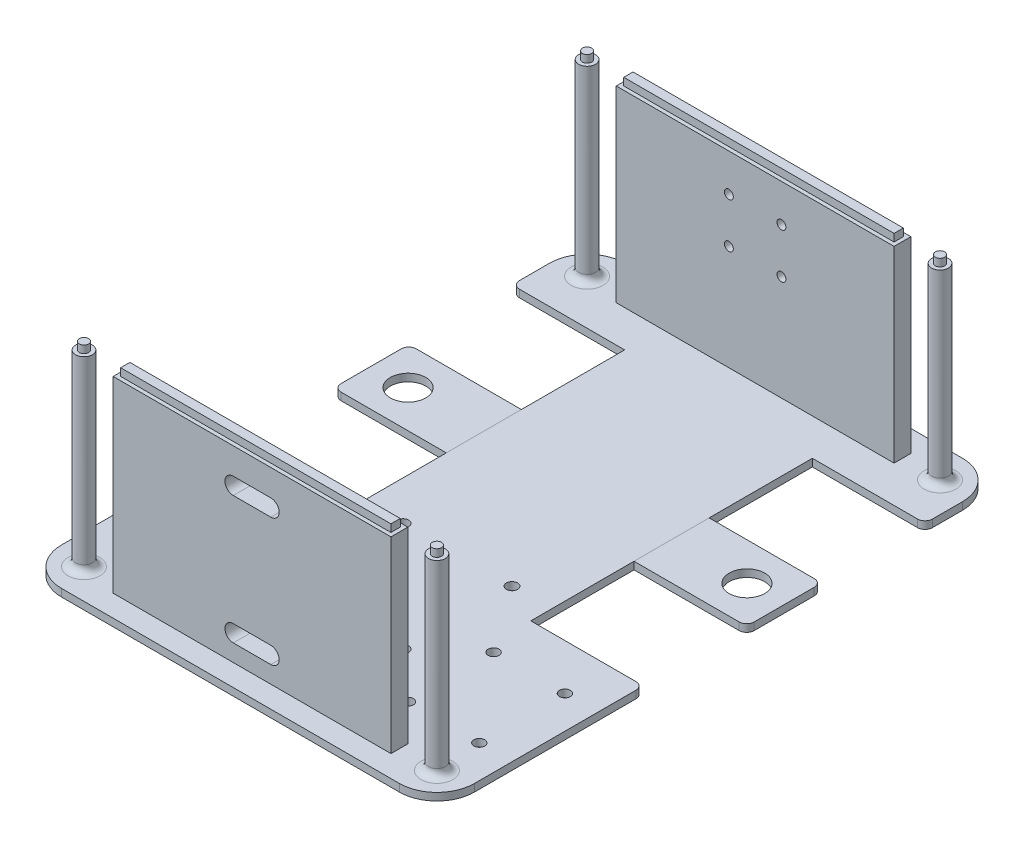
SolidWorks part; units mm, degrees
material "ABS"
ref_plane "Front Plane" through (0, 0, 0) normal (0, 0, 1) x (1, 0, 0)
ref_plane "Top Plane" through (0, 0, 0) normal (0, 1, 0) x (1, 0, 0)
ref_plane "Right Plane" through (0, 0, 0) normal (1, 0, 0) x (0, 0, -1)
sketch "Sketch2" plane through (0, 0, 0) normal (0, 1, 0) x (1, 0, 0)
  line L0 (-148.7583, 0) -> (98.0966, 0) construction
  line L1 (-69.85, -95.25) -> (69.85, -95.25)
  line L2 (-69.85, -95.25) -> (-69.85, 95.25)
  line L3 (-69.85, 95.25) -> (69.85, 95.25)
  line L4 (69.85, -95.25) -> (69.85, 95.25)
  line L5 (-69.85, -95.25) -> (69.85, 95.25) construction
  line L6 (-69.85, 95.25) -> (69.85, -95.25) construction
  line L7 (0, 121.1686) -> (0, -125.6862) construction
  point P0 (0, 0)
  dimension "D1" = 190.5
  dimension "D2" = 139.7
extrude "Base Plate" add sketch "Sketch2" along normal blind 2.54
sketch "Sketch4" plane through (0, 2.54, 0) normal (0, 1, 0) x (1, 0, 0)
  line L0 (0, -95.25) -> (0, 95.25) construction
  line L1 (-69.85, -95.25) -> (69.85, -95.25) construction
  line L2 (69.85, 95.25) -> (-69.85, 95.25) construction
  line L3 (-34.66, -69.85) -> (-34.66, -40.894) construction
  line L4 (-34.66, -40.894) -> (-58.79, -40.894) construction
  line L5 (-58.79, -40.894) -> (-58.79, -69.85) construction
  line L6 (-58.79, -69.85) -> (-34.66, -69.85) construction
  line L7 (69.85, -95.25) -> (69.85, 95.25) construction
  line L8 (-69.85, 95.25) -> (-69.85, -95.25) construction
  circle A0 centre (-58.79, -69.85) radius 1.8415
  circle A1 centre (-34.66, -69.85) radius 1.8415
  circle A2 centre (-34.66, -40.894) radius 1.8415
  circle A3 centre (-58.79, -40.894) radius 1.8415
  circle A4 centre (34.66, -69.85) radius 1.8415
  circle A5 centre (58.79, -69.85) radius 1.8415
  circle A6 centre (58.79, -40.894) radius 1.8415
  circle A7 centre (34.66, -40.894) radius 1.8415
  point P0 (-58.79, -69.85)
  point P1 (-58.79, -40.894)
  point P2 (-34.66, -40.894)
  point P3 (-34.66, -69.85)
  dimension "D4" = 3.683
  dimension "D1" = 28.956
  dimension "D2" = 24.13
  dimension "D3" = 11.06
  dimension "D5" = 25.4
extrude "L-Bracket holes" cut sketch "Sketch4" against normal blind 6.35
sketch "Sketch5" plane through (0, 2.54, 0) normal (0, 1, 0) x (1, 0, 0)
  line L0 (-69.85, -25.4) -> (-31.75, -25.4)
  line L1 (-69.85, 95.25) -> (-69.85, -95.25) construction
  line L2 (-31.75, -25.4) -> (-31.75, 69.85)
  line L3 (-31.75, 69.85) -> (-69.85, 69.85)
  line L4 (-69.85, 69.85) -> (-69.85, -25.4)
  line L5 (-69.85, -95.25) -> (69.85, -95.25) construction
  line L6 (69.85, 95.25) -> (-69.85, 95.25) construction
  line L7 (0, -95.25) -> (0, 95.25) construction
  line L8 (-58.79, -40.894) -> (-34.66, -40.894) construction
  line L9 (31.75, 69.85) -> (69.85, 69.85)
  line L10 (31.75, -25.4) -> (31.75, 69.85)
  line L11 (69.85, -25.4) -> (31.75, -25.4)
  line L12 (69.85, 69.85) -> (69.85, -25.4)
  dimension "D1" = 25.4
  dimension "D2" = 95.25
  dimension "D3" = 38.1
extrude "Steering Wheels Holes" cut sketch "Sketch5" against normal blind 6.35
fillet "Fillet1" radius 12.7 4 edges at (69.85, 1.27, -95.25) (-69.85, 1.27, -95.25) (69.85, 1.27, 95.25) (-69.85, 1.27, 95.25)
fillet "Fillet2" radius 2.54 4 edges at (69.85, 1.27, -69.85) (69.85, 1.27, 25.4) (-69.85, 1.27, 25.4) (-69.85, 1.27, -69.85)
sketch "Sketch6" plane through (0, 2.54, 0) normal (0, 1, 0) x (1, 0, 0)
  line L0 (-69.85, -95.25) -> (-69.85, 95.25) construction
  line L1 (-69.85, -95.25) -> (69.85, -95.25) construction
  line L2 (0, -88.935) -> (0, 95.5267) construction
  line L3 (-69.85, -27.94) -> (69.85, -27.94) construction
  point P0 (-59.69, -85.09)
  point P12 (-59.69, 29.21)
  point P13 (59.69, -85.09)
  point P14 (59.69, 29.21)
  dimension "D1" = 10.16
  dimension "D2" = 10.16
sketch "Sketch13" plane through (0, 2.54, 0) normal (0, 1, 0) x (1, 0, 0)
  line L0 (-69.85, -55.245) -> (69.85, -55.245) construction
  line L2 (-69.85, -27.94) -> (-69.85, -82.55) construction
  line L3 (69.85, -82.55) -> (69.85, -27.94) construction
  line L5 (-34.66, -69.85) -> (-34.66, -40.894) construction
  line L6 (34.66, -69.85) -> (34.66, -40.894) construction
  line L7 (-18.415, -55.245) -> (18.415, -55.245) construction
  line L8 (18.415, -55.245) -> (18.415, -18.415) construction
  line L9 (18.415, -18.415) -> (-18.415, -18.415) construction
  line L10 (-18.415, -18.415) -> (-18.415, -55.245) construction
  circle A0 centre (-18.415, -18.415) radius 1.905
  circle A1 centre (-18.415, -55.245) radius 1.905
  circle A2 centre (18.415, -55.245) radius 1.905
  circle A3 centre (18.415, -18.415) radius 1.905
  dimension "D1" = 3.81
  dimension "D4" = 36.83
  dimension "D5" = 36.83
extrude "Holes for L298" cut sketch "Sketch13" against normal blind 6.35
sketch "Sketch14" plane through (0, 2.54, 0) normal (0, 1, 0) x (1, 0, 0)
  line L0 (11.2203, 34.01) -> (-11.2203, 34.01)
  line L1 (11.2203, 5.61) -> (-11.2203, 5.61)
  line L2 (11.2203, 5.61) -> (11.2203, 10.44)
  line L3 (11.2203, 10.44) -> (-11.2203, 10.44)
  line L4 (0, 95.25) -> (0, -56.8347) construction
  line L5 (57.15, 95.25) -> (-57.15, 95.25) construction
  line L6 (-11.2203, 5.61) -> (-11.2203, 10.44)
  line L7 (-31.75, 22.225) -> (31.75, 22.225) construction
  line L8 (-31.75, -25.4) -> (-31.75, 69.85) construction
  line L9 (31.75, 69.85) -> (31.75, -25.4) construction
  line L10 (11.2203, 5.61) -> (-11.2203, 10.44) construction
  line L11 (11.2203, 10.44) -> (-11.2203, 5.61) construction
  line L12 (-11.2203, 38.84) -> (-11.2203, 34.01)
  line L13 (11.2203, 38.84) -> (-11.2203, 38.84)
  line L14 (11.2203, 38.84) -> (11.2203, 34.01)
  circle A2 centre (0, 8.025) radius 0.9906
  circle A3 centre (0, 36.425) radius 0.9906
  dimension "D3" = 4.83
  dimension "D2" = 1.9812
  dimension "D1" = 14.2
extrude "Cut-Extrude4" cut sketch "Sketch14" against normal blind 6.35
sketch "Sketch15" plane through (0, 2.54, 0) normal (0, 1, 0) x (1, 0, 0)
  line L0 (-69.85, -95.25) -> (-69.85, 95.25) construction
  line L1 (-69.85, 95.25) -> (69.85, 95.25) construction
  line L2 (0, 95.25) -> (0, 49.0943) construction
  line L3 (0, 121.1686) -> (0, -125.6862) construction
  circle A0 centre (-59.69, 85.09) radius 1.57
  circle A1 centre (-59.69, 85.09) radius 2.84
  point P0 (-59.69, 85.09)
  point P5 (59.69, 85.09)
  dimension "D3" = 3.14
  dimension "D1" = 10.16
  dimension "D2" = 10.16
  dimension "D4" = 1.27
extrude "Boss-Extrude3" add sketch "Sketch15" along normal blind 63.5
extrude "Boss-Extrude4" add sketch "Sketch15<2>" along normal blind 66.04 contours A0 region at (-59.69, 2.54, -85.09)
sketch "Sketch15<2>" plane through (0, 2.54, 0) normal (0, 1, 0) x (1, 0, 0) same geometry as "Sketch15"
mirror "Mirror1" about plane through (0, 0, 0) normal (1, 0, 0) of "Boss-Extrude4"
mirror "Mirror2" about plane through (0, 0, 0) normal (1, 0, 0) of "Boss-Extrude3"
sketch "Sketch23" plane through (0, 2.54, 0) normal (0, 1, 0) x (1, 0, 0)
  line L0 (0, 95.25) -> (0, -95.25) construction
  line L1 (-69.85, -27.94) -> (-69.85, -82.55) construction
  line L2 (-57.15, -95.25) -> (57.15, -95.25) construction
  circle A0 centre (-59.69, -85.09) radius 1.57
  circle A1 centre (-59.69, -85.09) radius 2.84
  dimension "D1" = 3.14
  dimension "D3" = 10.16
  dimension "D4" = 10.16
  dimension "D2" = 1.27
extrude "Boss-Extrude5" add sketch "Sketch23" along normal blind 63.5
extrude "Boss-Extrude6" add sketch "Sketch23<2>" along normal blind 66.04 contours A0 region at (-59.69, 2.54, 85.09)
sketch "Sketch23<2>" plane through (0, 2.54, 0) normal (0, 1, 0) x (1, 0, 0) same geometry as "Sketch23"
mirror "Mirror3" about plane through (0, 0, 0) normal (1, 0, 0) of "Boss-Extrude6", "Boss-Extrude5"
sketch "Sketch24" plane through (0, 2.54, 0) normal (0, 1, 0) x (1, 0, 0)
  line L0 (-59.69, -87.93) -> (59.69, -87.93) construction
  line L1 (-59.69, -82.25) -> (59.69, -82.25) construction
  line L2 (-59.69, 82.25) -> (59.69, 82.25) construction
  line L3 (-46.99, -87.93) -> (46.99, -87.93)
  line L4 (-46.99, -87.93) -> (-46.99, -82.25)
  line L5 (-46.99, -82.25) -> (46.99, -82.25)
  line L6 (46.99, -87.93) -> (46.99, -82.25)
  line L7 (59.69, 87.93) -> (-59.69, 87.93) construction
  line L9 (-46.99, 82.25) -> (46.99, 82.25)
  line L10 (-46.99, 82.25) -> (-46.99, 87.93)
  line L11 (-46.99, 87.93) -> (46.99, 87.93)
  line L12 (46.99, 82.25) -> (46.99, 87.93)
  circle A0 centre (-59.69, -85.09) radius 2.84 construction
  circle A1 centre (59.69, -85.09) radius 2.84 construction
  circle A2 centre (-59.69, -85.09) radius 2.84 construction
  circle A3 centre (-59.69, 85.09) radius 2.84 construction
  circle A4 centre (-59.69, 85.09) radius 2.84 construction
  circle A5 centre (59.69, 85.09) radius 2.84 construction
  circle A6 centre (59.69, 85.09) radius 2.84 construction
  dimension "D1" = 12.7
  dimension "D2" = 12.7
  dimension "D3" = 12.7
  dimension "D4" = 12.7
extrude "Boss-Extrude7" add sketch "Sketch24" along normal blind 63.5
sketch "Sketch25" plane through (0, 66.04, 0) normal (0, 1, 0) x (1, 0, 0)
  line L8 (-45.72, -83.52) -> (-45.72, -86.66)
  line L9 (-45.72, -86.66) -> (45.72, -86.66)
  line L10 (45.72, -86.66) -> (45.72, -83.52)
  line L11 (45.72, -83.52) -> (-45.72, -83.52)
  line L12 (-45.72, -83.52) -> (-45.72, -86.66)
  line L13 (-45.72, -86.66) -> (45.72, -86.66)
  line L14 (45.72, -86.66) -> (45.72, -83.52)
  line L15 (45.72, -83.52) -> (-45.72, -83.52)
  line L20 (-45.72, 86.66) -> (-45.72, 83.52)
  line L21 (-45.72, 83.52) -> (45.72, 83.52)
  line L22 (45.72, 83.52) -> (45.72, 86.66)
  line L23 (45.72, 86.66) -> (-45.72, 86.66)
  line L24 (-45.72, 86.66) -> (-45.72, 83.52)
  line L25 (-45.72, 83.52) -> (45.72, 83.52)
  line L26 (45.72, 83.52) -> (45.72, 86.66)
  line L27 (45.72, 86.66) -> (-45.72, 86.66)
  dimension "D1" = 1.27
  dimension "D2" = 1.27
extrude "Boss-Extrude8" add sketch "Sketch25" along normal blind 2.54
sketch "Sketch26" plane through (0, 0, -87.93) normal (0, 0, -1) x (-1, 0, 0)
  line L0 (0, 66.04) -> (0, 83.3576) construction
  line L1 (-46.99, 66.04) -> (46.99, 66.04) construction
  line L2 (-8.89, 53.34) -> (-8.89, -5.4923) construction
  circle A0 centre (-8.89, 53.34) radius 1.5
  circle A1 centre (-8.89, 38.1) radius 1.5
  circle A2 centre (8.89, 38.1) radius 1.5
  circle A3 centre (8.89, 53.34) radius 1.5
  dimension "D1" = 3
  dimension "D3" = 3
  dimension "D2" = 8.89
  dimension "D4" = 15.24
  dimension "D5" = 12.7
extrude "Cut-Extrude5" cut sketch "Sketch26" against normal up to next (5.68 mm away)
sketch "Sketch27" plane through (0, 2.54, 0) normal (0, 1, 0) x (1, 0, 0)
  line L0 (-31.75, -25.4) -> (-31.75, 69.85) construction
  line L1 (-31.75, 9.525) -> (-69.85, 9.525)
  line L2 (-31.75, 9.525) -> (-31.75, 34.925)
  line L3 (-31.75, 34.925) -> (-69.85, 34.925)
  line L4 (-69.85, 9.525) -> (-69.85, 34.925)
  line L5 (-69.85, -27.94) -> (-69.85, -82.55) construction
  line L6 (31.75, 22.225) -> (-61.2417, 22.225) construction
  line L7 (31.75, 69.85) -> (31.75, -25.4) construction
  line L8 (0, -95.25) -> (0, 114.9927) construction
  line L9 (-57.15, -95.25) -> (57.15, -95.25) construction
  line L10 (31.75, 34.925) -> (69.85, 34.925)
  line L11 (69.85, 9.525) -> (69.85, 34.925)
  line L12 (31.75, 9.525) -> (69.85, 9.525)
  line L13 (31.75, 9.525) -> (31.75, 34.925)
  point P13 (-31.75, 22.225)
  dimension "D1" = 25.4
extrude "Boss-Extrude9" add sketch "Sketch27" against normal through all separate body
sketch "Sketch28" plane through (0, 2.54, 0) normal (0, 1, 0) x (1, 0, 0)
  line L0 (0, -95.25) -> (0, 140.3564) construction
  line L1 (69.85, 9.525) -> (69.85, 34.925) construction
  circle A0 centre (57.3106, 22.1602) radius 6
  circle A1 centre (-57.3106, 22.1602) radius 6
  dimension "D1" = 12
  dimension "D2" = 12.5394
extrude "Cut-Extrude6" cut sketch "Sketch28" against normal through all
fillet "Fillet4" radius 2.54 2 edges at (69.85, 1.27, -34.925) (69.85, 1.27, -9.525)
fillet "Fillet5" radius 2.54 2 edges at (-69.85, 1.27, -34.925) (-69.85, 1.27, -9.525)
sketch "Sketch29" plane through (0, 2.54, 0) normal (0, 1, 0) x (1, 0, 0)
  line L0 (31.75, 22.225) -> (-61.2417, 22.225) construction
  line L1 (14.7459, -2.7347) -> (-14.7459, -2.7347)
  line L2 (14.7459, -2.7347) -> (14.7459, 47.1847)
  line L3 (14.7459, 47.1847) -> (-14.7459, 47.1847)
  line L4 (-14.7459, -2.7347) -> (-14.7459, 47.1847)
  line L5 (14.7459, -2.7347) -> (-14.7459, 47.1847) construction
  line L6 (14.7459, 47.1847) -> (-14.7459, -2.7347) construction
  line L7 (0, -95.25) -> (0, 114.9927) construction
  point P0 (0, 22.225)
extrude "Boss-Extrude10" add sketch "Sketch29" against normal blind 2.54
fillet "Fillet6" radius 2.54 4 edges at (-59.69, 2.54, -87.93) (-59.69, 2.54, 82.25) (59.69, 2.54, -82.25) (59.69, 2.54, 87.93)
sketch "Sketch33" plane through (0, 0, 87.93) normal (0, 0, 1) x (1, 0, 0)
  line L0 (0, 66.04) -> (0, -27.2223) construction
  line L1 (-46.99, 66.04) -> (46.99, 66.04) construction
  line L2 (-6.35, 54.3061) -> (6.35, 54.3061) construction
  line L3 (-6.35, 11.1261) -> (6.35, 11.1261) construction
  line L4 (-6.35, 11.1261) -> (-6.35, 54.3061) construction
  line L5 (-6.35, 54.3061) -> (6.35, 54.3061) construction
  line L6 (6.35, 11.1261) -> (6.35, 54.3061) construction
  line L7 (-6.35, 11.1261) -> (6.35, 54.3061) construction
  line L8 (-6.35, 54.3061) -> (6.35, 11.1261) construction
  line L9 (-6.35, 57.127) -> (6.35, 57.127)
  line L10 (-6.35, 51.4853) -> (6.35, 51.4853)
  line L11 (-6.35, 32.7161) -> (80.4679, 32.7161) construction
  line L12 (-6.35, 11.1261) -> (6.35, 11.1261) construction
  line L13 (-6.35, 8.3053) -> (6.35, 8.3053)
  line L14 (-6.35, 13.947) -> (6.35, 13.947)
  arc A0 (-6.35, 57.127) -> (-6.35, 51.4853) centre (-6.35, 54.3061) ccw
  arc A1 (6.35, 51.4853) -> (6.35, 57.127) centre (6.35, 54.3061) ccw
  arc A2 (-6.35, 8.3053) -> (-6.35, 13.947) centre (-6.35, 11.1261) cw
  arc A3 (6.35, 13.947) -> (6.35, 8.3053) centre (6.35, 11.1261) cw
  point P5 (0, 32.7161)
  point P10 (0, 54.3061)
  point P17 (0, 11.1261)
  dimension "D1" = 43.18
  dimension "D2" = 6.35
extrude "Cut-Extrude7" cut sketch "Sketch33" against normal up to next (5.68 mm away)
